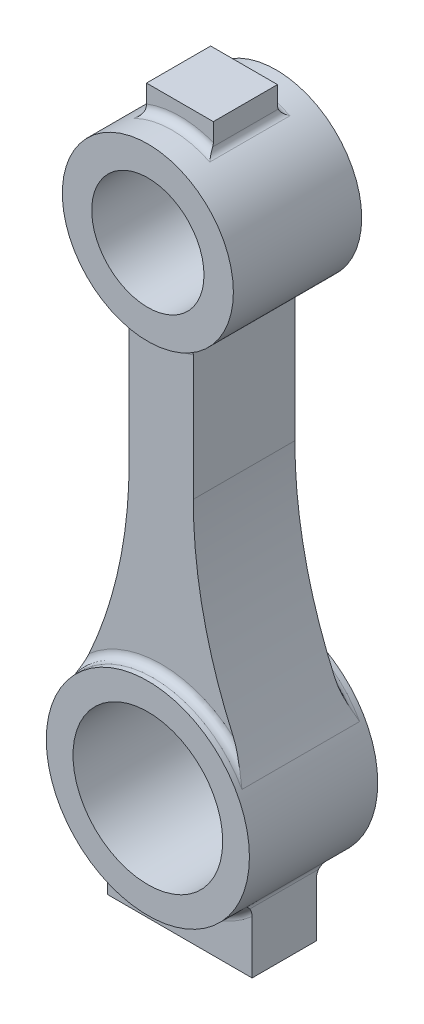
SolidWorks part; units mm, degrees
ref_plane "Front Plane" through (0, 0, 0) normal (0, 0, 1) x (1, 0, 0)
ref_plane "Top Plane" through (0, 0, 0) normal (0, 1, 0) x (1, 0, 0)
ref_plane "Right Plane" through (0, 0, 0) normal (1, 0, 0) x (0, 0, -1)
sketch "Sketch2" plane through (0, 0, 0) normal (0, 0, 1) x (1, 0, 0)
  circle A0 centre (0, 0) radius 19
  circle A1 centre (0, 0) radius 14
  circle A2 centre (0, 90) radius 16
  circle A3 centre (0, 90) radius 10.5
  point P7 (0, 0)
  point P8 (0, 0)
  dimension "D1" = 28
  dimension "D2" = 38
  dimension "D3" = 21
  dimension "D4" = 32
  dimension "D5" = 90
extrude "Boss-Extrude1" add sketch "Sketch2" along normal mid plane 24
sketch "Sketch3" plane through (0, 0, 0) normal (0, 0, 1) x (1, 0, 0)
  line L0 (6, 75.1676) -> (6, 50.1676)
  line L1 (0, 90) -> (0, 59.2973) construction
  line L2 (-6, 75.1676) -> (-6, 50.1676)
  circle A0 centre (0, 0) radius 19 construction
  circle A1 centre (0, 90) radius 16 construction
  arc A2 (16.6089, 9.2274) -> (-16.6089, 9.2274) centre (0, 0) ccw
  arc A3 (-6, 75.1676) -> (6, 75.1676) centre (0, 90) ccw
  arc A4 (6, 50.1676) -> (16.6089, 9.2274) centre (90.2996, 50.1676) ccw
  arc A5 (-6, 50.1676) -> (-16.6089, 9.2274) centre (-90.2996, 50.1676) cw
  point P12 (0, 0)
  dimension "D1" = 25
extrude "Boss-Extrude2" add sketch "Sketch3" along normal mid plane 19
sketch "Sketch4" plane through (0, 0, 0) normal (0, 0, 1) x (1, 0, 0)
  line L0 (0, 117.5897) -> (0, -32.1777) construction
  line L1 (-6.25, 104.7288) -> (-6.25, 109.7288)
  line L2 (6.25, 104.7288) -> (6.25, 109.7288)
  line L3 (-6.25, 109.7288) -> (6.25, 109.7288)
  line L4 (-13.5, -13.3697) -> (-13.5, -25.3697)
  line L5 (13.5, -13.3697) -> (13.5, -25.3697)
  line L6 (-13.5, -25.3697) -> (13.5, -25.3697)
  circle A0 centre (0, 90) radius 16 construction
  arc A1 (0, 74) -> (-6.25, 104.7288) centre (0, 90) ccw
  circle A2 centre (0, 0) radius 19 construction
  arc A3 (0, 19) -> (13.5, -13.3697) centre (0, 0) ccw
  dimension "D1" = 5
  dimension "D2" = 12.5
  dimension "D3" = 12
  dimension "D4" = 27
extrude "Boss-Extrude3" add sketch "Sketch4" along normal mid plane 12 contours A3 L0 L6 L5 | L0 A3 L4 L6 | L3 L0 A1 L2 | L0 L3 L1 A1 region at (-3.2834, 107.6389, 0) region at (3.2834, 107.6389, 0) region at (7.5005, -21.1463, 0) region at (-7.5005, -21.1463, 0)
fillet "Fillet1" radius 1.5 8 edges at (-6.25, 104.7288, 0) (0, 106, -6) (6.25, 104.7288, 0) (0, 106, 6) (0, 19, 9.5) (0, 19, -9.5) (0, 74, -9.5) (0, 74, 9.5)
fillet "Fillet2" radius 1.5 4 edges at (13.5, -13.3697, 0) (0, -19, 6) (0, -19, -6) (-13.5, -13.3697, 0)
